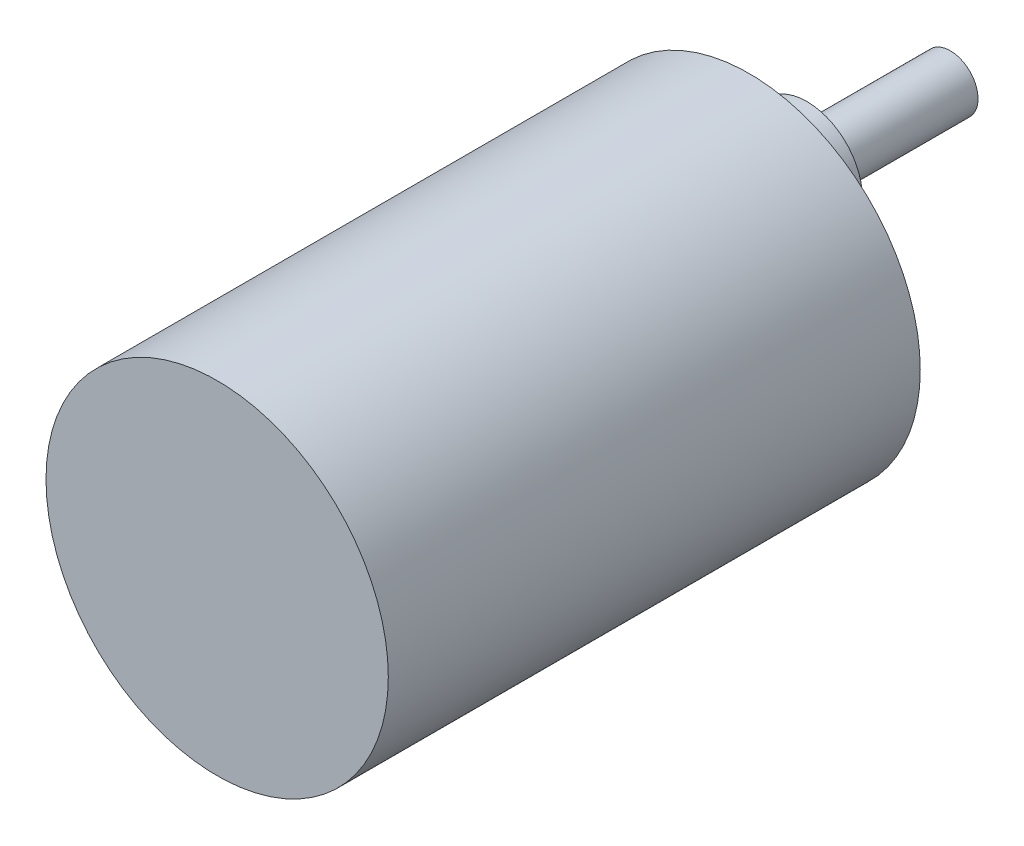
SolidWorks part; units mm, degrees
ref_plane "前视基准面" through (0, 0, 0) normal (0, 0, 1) x (1, 0, 0)
ref_plane "上视基准面" through (0, 0, 0) normal (0, 1, 0) x (1, 0, 0)
ref_plane "右视基准面" through (0, 0, 0) normal (1, 0, 0) x (0, 0, -1)
sketch "草图1" plane through (0, 0, 0) normal (0, 0, 1) x (1, 0, 0)
  line L0 (0, 0) -> (15.4904, -0.5459) construction
  circle A0 centre (0, 0) radius 18.5
  circle A1 centre (15.4904, -0.5459) radius 1.5
  circle A2 centre (7.2724, -13.688) radius 1.5
  circle A3 centre (-8.218, -13.1421) radius 1.5
  circle A4 centre (-15.4904, 0.5459) radius 1.5
  circle A5 centre (-7.2724, 13.688) radius 1.5
  circle A6 centre (8.218, 13.1421) radius 1.5
  point P17 (0, 0)
  dimension "D1" = 6
extrude "凸台-拉伸1" add sketch "草图1" along normal blind 46 contours A0 A6 A5 A4 A3 A2 A1 | A4 | A5 | A3 | A2 | A1 | A6 region at (0, 0, 0) region at (15.4904, -0.5459, 0) region at (7.2724, -13.688, 0) region at (-8.218, -13.1421, 0) region at (-15.4904, 0.5459, 0) region at (-7.2724, 13.688, 0) region at (8.218, 13.1421, 0)
extrude "切除-拉伸1" cut sketch "草图1<3>" along normal blind 6 contours A2 | A3 | A4 | A6 | A5 | A1 region at (7.2724, -13.688, 0) region at (-8.218, -13.1421, 0) region at (-15.4904, 0.5459, 0) region at (-7.2724, 13.688, 0) region at (8.218, 13.1421, 0)
sketch "草图1<3>" plane through (0, 0, 0) normal (0, 0, 1) x (1, 0, 0) same geometry as "草图1"
ref_plane "基准面4" through (0, 0, 0) normal (0, 0, -1) x (-1, 0, 0)
sketch "草图2" plane through (0, 0, 0) normal (0, 0, -1) x (-1, 0, 0)
  line L0 (15.4904, 0.5459) -> (-15.4904, -0.5459) construction
  line L1 (0, 0) -> (-0.2465, 6.9957) construction
  circle A0 centre (-0.2465, 6.9957) radius 6
extrude "凸台-拉伸2" add sketch "草图2" along normal blind 6
ref_plane "基准面5" through (0, 0, -6) normal (0, 0, -1) x (-1, 0, 0)
sketch "草图3" plane through (0, 0, -6) normal (0, 0, -1) x (-1, 0, 0)
  circle A0 centre (-0.2465, 6.9957) radius 3
extrude "凸台-拉伸3" add sketch "草图3" along normal blind 15.5
ref_plane "基准面6" through (0, 0, 46) normal (0, 0, 1) x (1, 0, 0)
sketch "草图5" plane through (0, 0, 46) normal (0, 0, 1) x (1, 0, 0)
  circle A1 centre (0, 0) radius 18.5
  circle A2 centre (0, 0) radius 18.5
  dimension "D1" = 0
extrude "凸台-拉伸4" add sketch "草图5" along normal blind 11.5
